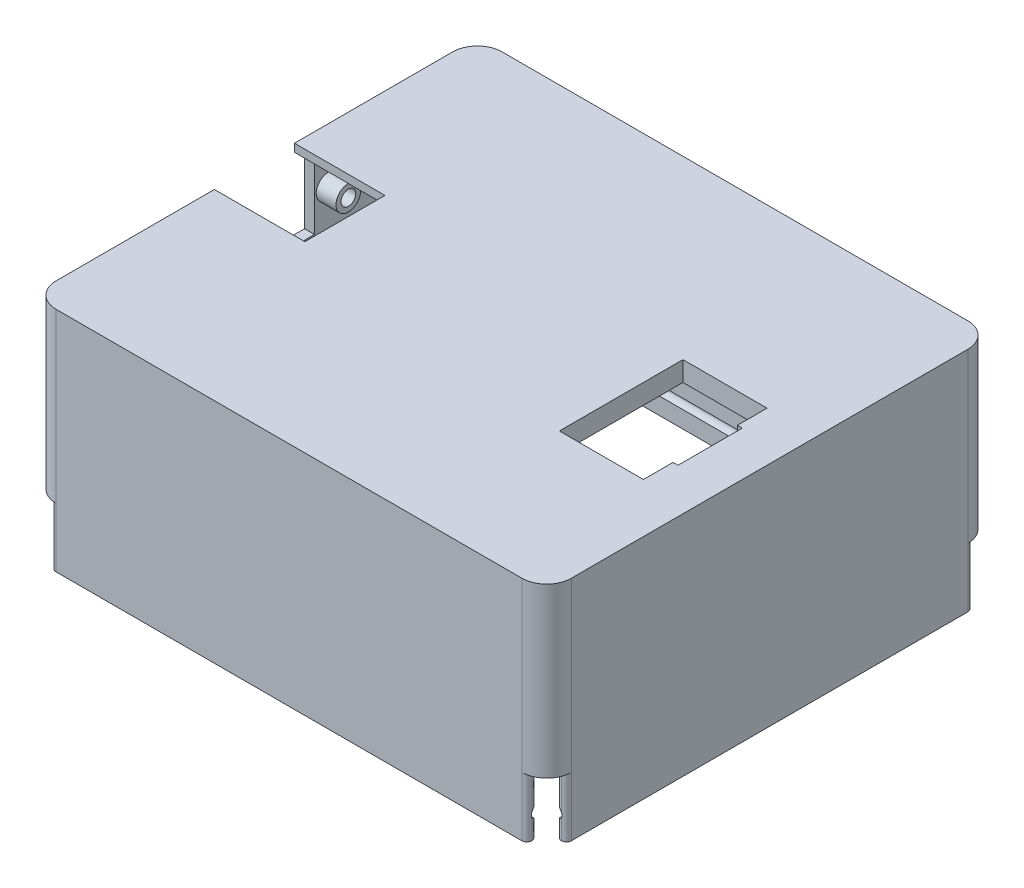
SolidWorks part; units mm, degrees
ref_plane "Plan de face" through (0, 0, 0) normal (0, 0, 1) x (1, 0, 0)
ref_plane "Plan de dessus" through (0, 0, 0) normal (0, 1, 0) x (1, 0, 0)
ref_plane "Plan de droite" through (0, 0, 0) normal (1, 0, 0) x (0, 0, -1)
sketch "Esquisse1" plane through (0, 0, 0) normal (0, 1, 0) x (1, 0, 0)
  line L1 (-52.1, -45.1) -> (52.1, -45.1)
  line L2 (-52.1, -45.1) -> (-52.1, 45.1)
  line L3 (-52.1, 45.1) -> (52.1, 45.1)
  line L4 (52.1, -45.1) -> (52.1, 45.1)
  line L5 (-52.1, -45.1) -> (52.1, 45.1) construction
  line L6 (-52.1, 45.1) -> (52.1, -45.1) construction
  point P0 (0, 0)
  dimension "D1" = 104.2
  dimension "D2" = 90.2
extrude "Boss.-Extru.1" add sketch "Esquisse1" along normal blind 2
sketch "Esquisse2" plane through (0, 0, 0) normal (0, -1, 0) x (1, 0, 0)
  line L8 (50.1, -43.1) -> (50.1, 43.1)
  line L9 (50.1, 43.1) -> (-50.1, 43.1)
  line L10 (-50.1, 43.1) -> (-50.1, -43.1)
  line L11 (-50.1, -43.1) -> (50.1, -43.1)
  line L12 (50.1, -43.1) -> (50.1, 43.1)
  line L13 (50.1, 43.1) -> (-50.1, 43.1)
  line L14 (-50.1, 43.1) -> (-50.1, -43.1)
  line L15 (-50.1, -43.1) -> (50.1, -43.1)
  line L16 (52.1, -45.1) -> (52.1, 45.1)
  line L17 (52.1, 45.1) -> (-52.1, 45.1)
  line L18 (-52.1, 45.1) -> (-52.1, -45.1)
  line L19 (-52.1, -45.1) -> (52.1, -45.1)
  line L20 (52.1, -45.1) -> (52.1, 45.1)
  line L21 (52.1, 45.1) -> (-52.1, 45.1)
  line L22 (-52.1, 45.1) -> (-52.1, -45.1)
  line L23 (-52.1, -45.1) -> (52.1, -45.1)
  dimension "D1" = 2
  dimension "D2" = 0
extrude "Boss.-Extru.2" add sketch "Esquisse2" along normal blind 44
sketch "Esquisse3" plane through (0, -44, 0) normal (0, -1, 0) x (1, 0, 0)
  line L0 (-50.1, 41.1) -> (-50.1, 43.1)
  line L1 (-52.1, 45.1) -> (-48.1, 45.1)
  line L2 (-52.1, 45.1) -> (-52.1, 41.1)
  line L3 (-52.1, 41.1) -> (-50.1, 41.1)
  line L4 (-48.1, 45.1) -> (-48.1, 43.1)
  line L5 (-50.1, 43.1) -> (-48.1, 43.1)
  dimension "D1" = 4
  dimension "D2" = 4
  dimension "D3" = 2
  dimension "D4" = 2
extrude "Enlèv. mat.-Extru.1" cut sketch "Esquisse3" against normal blind 12
mirror "Symétrie1" about plane through (0, 0, 0) normal (0, 0, 1) of "Enlèv. mat.-Extru.1"
mirror "Symétrie2" about plane through (0, 0, 0) normal (1, 0, 0) of "Symétrie1"
fillet "Congé3" radius 1 16 edges at (-48.1, -38, 45.1) (-48.1, -38, 43.1) (-50.1, -38, 41.1) (-52.1, -38, 41.1) (48.1, -38, 45.1) (48.1, -38, 43.1) (52.1, -38, 41.1) (50.1, -38, 41.1) (52.1, -38, -41.1) (50.1, -38, -41.1) (48.1, -38, -43.1) (48.1, -38, -45.1) (-48.1, -38, -45.1) (-48.1, -38, -43.1) (-50.1, -38, -41.1) (-52.1, -38, -41.1)
fillet "Congé1" radius 5 4 edges at (52.1, -15, 45.1) (52.1, -15, -45.1) (-52.1, -15, -45.1) (-52.1, -15, 45.1)
sketch "Esquisse4" plane through (0, 0, 0) normal (1, 0, 0) x (0, 0, -1)
  line L0 (-43.1, -32) -> (-43.1, -44) construction
  line L1 (-43.1, -38.4) -> (-43.1, -40.6)
  line L2 (-44.1, -44) -> (-43.1, -44) construction
  arc A1 (-43.1, -38.4) -> (-43.1, -40.6) centre (-43.1, -39.5) ccw
  dimension "D1" = 1.1
  dimension "D2" = 4.5
extrude "Enlèv. mat.-Extru.2" cut sketch "Esquisse4" against normal through all both and the other way through all
mirror "Symétrie4" about plane through (0, 0, 0) normal (0, 0, 1) of "Enlèv. mat.-Extru.2"
sketch "Esquisse5" plane through (0, 0, 0) normal (0, 0, 1) x (1, 0, 0)
  line L0 (-50.1, -32) -> (-50.1, -44) construction
  line L1 (-51.1, -44) -> (-50.1, -44) construction
  line L2 (-50.1, -38.4) -> (-50.1, -40.6)
  arc A0 (-50.1, -38.4) -> (-50.1, -40.6) centre (-50.1, -39.5) ccw
  dimension "D1" = 1.1
  dimension "D2" = 4.5
extrude "Enlèv. mat.-Extru.3" cut sketch "Esquisse5" against normal through all both and the other way through all
mirror "Symétrie5" about plane through (0, 0, 0) normal (1, 0, 0) of "Enlèv. mat.-Extru.3"
sketch "Esquisse6" plane through (-52.1, 0, 0) normal (-1, 0, 0) x (0, 0, 1)
  line L0 (0, 15.9382) -> (0, -19.3286) construction
  line L1 (-40.1, 2) -> (40.1, 2) construction
  line L2 (-10.15, -14) -> (10.15, -14)
  line L3 (-10.15, -14) -> (-10.15, 0)
  line L4 (-10.15, 0) -> (10.15, 0)
  line L5 (10.15, -14) -> (10.15, 0)
  line L6 (-10.15, -14) -> (10.15, 0) construction
  line L7 (-10.15, 0) -> (10.15, -14) construction
  point P3 (0, -7)
  dimension "D1" = 14
  dimension "D2" = 2
  dimension "D3" = 20.3
extrude "Enlèv. mat.-Extru.4" cut sketch "Esquisse6" against normal blind 5 and the other way through all
sketch "Esquisse7" plane through (-52.1, 0, 0) normal (-1, 0, 0) x (0, 0, 1)
  line L0 (0, 0) -> (0, 2) construction
  line L1 (-40.1, 2) -> (40.1, 2) construction
  line L3 (-8.1, 0) -> (8.1, 0)
  line L4 (-8.1, 0) -> (-8.1, 2)
  line L5 (-8.1, 2) -> (8.1, 2)
  line L6 (8.1, 0) -> (8.1, 2)
  line L7 (-8.1, 0) -> (8.1, 2) construction
  line L8 (-8.1, 2) -> (8.1, 0) construction
  point P7 (0, 1)
  dimension "D1" = 16.2
extrude "Enlèv. mat.-Extru.5" cut sketch "Esquisse7" against normal blind 18.3
sketch "Esquisse11" plane through (0, 0, 0) normal (0, 1, 0) x (1, 0, 0)
  line L0 (-52.1, 0) -> (-32.1, 0) construction
  line L1 (-52.1, 10.15) -> (-52.1, -10.15) construction
  line L3 (-52.1, 40.1) -> (-52.1, 8.1) construction
  line L4 (-52.1, -10.15) -> (-32.1, -10.15)
  line L5 (-52.1, -10.15) -> (-52.1, 10.15)
  line L6 (-52.1, 10.15) -> (-32.1, 10.15)
  line L7 (-32.1, -10.15) -> (-32.1, 10.15)
  line L8 (-52.1, -10.15) -> (-32.1, 10.15) construction
  line L9 (-52.1, 10.15) -> (-32.1, -10.15) construction
  point P6 (-42.1, 0)
  dimension "D1" = 20.3
  dimension "D2" = 20
extrude "Enlèv. mat.-Extru.8" cut sketch "Esquisse11" along normal blind 0.4
sketch "Esquisse15" plane through (0, -44, 0) normal (0, -1, 0) x (1, 0, 0)
  line L0 (-50.1, 40.1) -> (-50.1, -40.1) construction
  line L1 (50.3, -43.3) -> (-50.3, -43.3)
  line L2 (50.3, -43.3) -> (50.3, 43.3)
  line L3 (50.3, 43.3) -> (-50.3, 43.3)
  line L4 (-50.3, -43.3) -> (-50.3, 43.3)
  line L5 (50.3, -43.3) -> (-50.3, 43.3) construction
  line L6 (50.3, 43.3) -> (-50.3, -43.3) construction
  line L7 (47.1, 43.1) -> (-47.1, 43.1) construction
  point P0 (0, 0)
  dimension "D1" = 0.2
  dimension "D2" = 0.2
extrude "Enlèv. mat.-Extru.10" cut sketch "Esquisse15" against normal blind 4.5
sketch "Esquisse16" plane through (-52.1, 0, 0) normal (-1, 0, 0) x (0, 0, 1)
  circle A0 centre (-13, -7) radius 1.5
  dimension "D1" = 3
extrude "Enlèv. mat.-Extru.11" cut sketch "Esquisse16" against normal blind 4
mirror "Symétrie6" about plane through (0, 0, 0) normal (0, 0, 1) of "Enlèv. mat.-Extru.11"
sketch "Esquisse17" plane through (0, 2, 0) normal (0, 1, 0) x (1, 0, 0)
  line L0 (52.1, -40.1) -> (52.1, 40.1) construction
  line L1 (25.1, -15.5179) -> (42.1, -15.5179)
  line L2 (25.1, -15.5179) -> (25.1, 9.4821)
  line L3 (25.1, 9.4821) -> (42.1, 9.4821)
  line L4 (42.1, -15.5179) -> (42.1, 9.4821)
  line L5 (25.1, -15.5179) -> (42.1, 9.4821) construction
  line L6 (25.1, 9.4821) -> (42.1, -15.5179) construction
  point P0 (33.6, -3.0179)
  dimension "D1" = 25
  dimension "D2" = 17
  dimension "D3" = 10
extrude "Enlèv. mat.-Extru.12" cut sketch "Esquisse17" against normal up to next
sketch "Esquisse18" plane through (0, 0, 0) normal (0, -1, 0) x (1, 0, 0)
  line L0 (25.1, 15.5179) -> (42.1, 15.5179) construction
  line L1 (46.1, -24.4821) -> (21.1, -24.4821)
  line L2 (46.1, -24.4821) -> (46.1, 19.5179)
  line L3 (46.1, 19.5179) -> (21.1, 19.5179)
  line L4 (21.1, -24.4821) -> (21.1, 19.5179)
  line L5 (46.1, -24.4821) -> (21.1, 19.5179) construction
  line L6 (46.1, 19.5179) -> (21.1, -24.4821) construction
  line L7 (42.1, -9.4821) -> (25.1, -9.4821) construction
  line L8 (42.1, 15.5179) -> (42.1, -9.4821) construction
  line L9 (25.1, -9.4821) -> (25.1, 15.5179) construction
  line L10 (25.1, 15.5179) -> (42.1, 15.5179)
  line L11 (25.1, -9.4821) -> (25.1, 15.5179)
  line L12 (42.1, -9.4821) -> (25.1, -9.4821)
  line L13 (42.1, 15.5179) -> (42.1, -9.4821)
  point P0 (33.6, -2.4821)
  dimension "D1" = 4
  dimension "D2" = 15
  dimension "D3" = 4
  dimension "D4" = 4
extrude "Boss.-Extru.3" add sketch "Esquisse18" along normal blind 2
sketch "Esquisse19" plane through (0, -2, 0) normal (0, -1, 0) x (1, 0, 0)
  line L0 (33.6, 19.5179) -> (33.6, -24.4821) construction
  line L1 (46.1, 19.5179) -> (21.1, 19.5179) construction
  line L2 (21.1, -24.4821) -> (46.1, -24.4821) construction
  line L3 (25.1, -9.4821) -> (42.1, -9.4821) construction
  line L4 (25.1, 15.5179) -> (25.1, -9.4821) construction
  line L5 (42.1, -9.4821) -> (42.1, 15.5179) construction
  circle A0 centre (33.6, -21.8821) radius 0.85
  circle A1 centre (23.6, 7.9179) radius 0.85
  circle A2 centre (43.6, 7.9179) radius 0.85
  dimension "D1" = 1.7
  dimension "D3" = 1.7
  dimension "D6" = 1.7
  dimension "D2" = 12.4
  dimension "D4" = 17.4
  dimension "D5" = 1.5
  dimension "D7" = 1.5
extrude "Enlèv. mat.-Extru.13" cut sketch "Esquisse19" against normal blind 2
sketch "Esquisse20" plane through (-50.1, 0, 0) normal (1, 0, 0) x (0, 0, -1)
  circle A0 centre (-13, -7) radius 2.5
  circle A1 centre (13, -7) radius 2.5
  circle A2 centre (-13, -7) radius 1.5 construction
  circle A3 centre (-13, -7) radius 1.5
  circle A4 centre (13, -7) radius 1.5 construction
  circle A5 centre (13, -7) radius 1.5
  dimension "D1" = 5
  dimension "D2" = 5
extrude "Boss.-Extru.4" add sketch "Esquisse20" along normal blind 4
sketch "Esquisse21" plane through (0, 2, 0) normal (0, 1, 0) x (1, 0, 0)
  line L0 (25.1, -3.0179) -> (52.1, -3.0179) construction
  line L1 (25.1, 9.4821) -> (25.1, -15.5179) construction
  line L2 (52.1, -40.1) -> (52.1, 40.1) construction
  line L3 (42.1, -15.5179) -> (42.1, 9.4821) construction
  line L4 (43.1, -9.5179) -> (42.1, -9.5179)
  line L5 (43.1, -9.5179) -> (43.1, 3.4821)
  line L6 (43.1, 3.4821) -> (42.1, 3.4821)
  line L7 (42.1, -9.5179) -> (42.1, 3.4821)
  line L8 (43.1, -9.5179) -> (42.1, 3.4821) construction
  line L9 (43.1, 3.4821) -> (42.1, -9.5179) construction
  point P6 (42.6, -3.0179)
  dimension "D1" = 13
  dimension "D2" = 1
extrude "Enlèv. mat.-Extru.14" cut sketch "Esquisse21" against normal up to next
